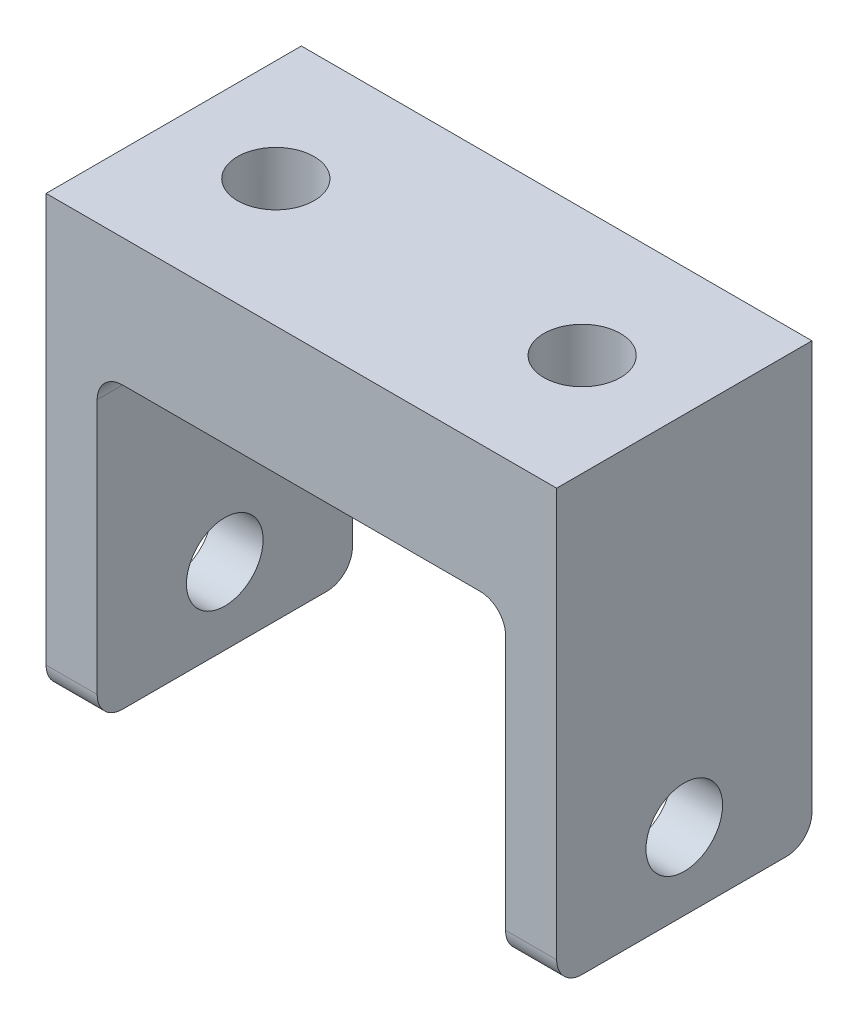
SolidWorks part; units mm, degrees
ref_plane "前视基准面" through (0, 0, 0) normal (0, 0, 1) x (1, 0, 0)
ref_plane "上视基准面" through (0, 0, 0) normal (0, 1, 0) x (1, 0, 0)
ref_plane "右视基准面" through (0, 0, 0) normal (1, 0, 0) x (0, 0, -1)
sketch "草图1" plane through (0, 0, 0) normal (0, 0, 1) x (1, 0, 0)
  line L0 (-6.8452, -5.9173) -> (-6.8452, 11.0827)
  line L1 (-6.8452, 11.0827) -> (13.1548, 11.0827)
  line L2 (13.1548, 11.0827) -> (13.1548, -5.9173)
  line L3 (13.1548, -5.9173) -> (11.1548, -5.9173)
  line L4 (11.1548, -5.9173) -> (11.1548, 6.0827)
  line L5 (11.1548, 6.0827) -> (-4.8452, 6.0827)
  line L6 (-4.8452, 6.0827) -> (-4.8452, -5.9173)
  line L7 (-4.8452, -5.9173) -> (-6.8452, -5.9173)
  dimension "D1" = 17
  dimension "D2" = 2
  dimension "D3" = 2
  dimension "D4" = 5
  dimension "D5" = 17
  dimension "D6" = 16
extrude "凸台-拉伸1" add sketch "草图1" along normal blind 10
sketch "草图2" plane through (13.1548, 0, 0) normal (1, 0, 0) x (0, 0, -1)
  line L1 (0, 11) -> (0, -11) construction
  line L2 (-10, -5.9173) -> (0, -5.9173) construction
  circle A0 centre (-5, -2.9173) radius 1.5
  dimension "D1" = 3
  dimension "D2" = 5
  dimension "D3" = 3
extrude "切除-拉伸1" cut sketch "草图2" against normal through all and the other way through all
sketch "草图3" plane through (0, 6.0827, 0) normal (0, -1, 0) x (1, 0, 0)
  line L2 (-4.8452, 10) -> (-4.8452, 0) construction
  line L3 (-4.8452, 10) -> (11.1548, 10) construction
  circle A0 centre (-2.8452, 5) radius 1.5
  circle A1 centre (9.1548, 5) radius 1.5
  dimension "D1" = 3
  dimension "D2" = 3
  dimension "D3" = 12
  dimension "D4" = 2
  dimension "D5" = 5
  dimension "D6" = 5
extrude "切除-拉伸2" cut sketch "草图3" against normal blind 10
fillet "圆角1" radius 1 6 edges at (11.1548, 6.0827, 5) (-4.8452, 6.0827, 5) (-5.8452, -5.9173, 0) (-5.8452, -5.9173, 10) (12.1548, -5.9173, 10) (12.1548, -5.9173, 0)
